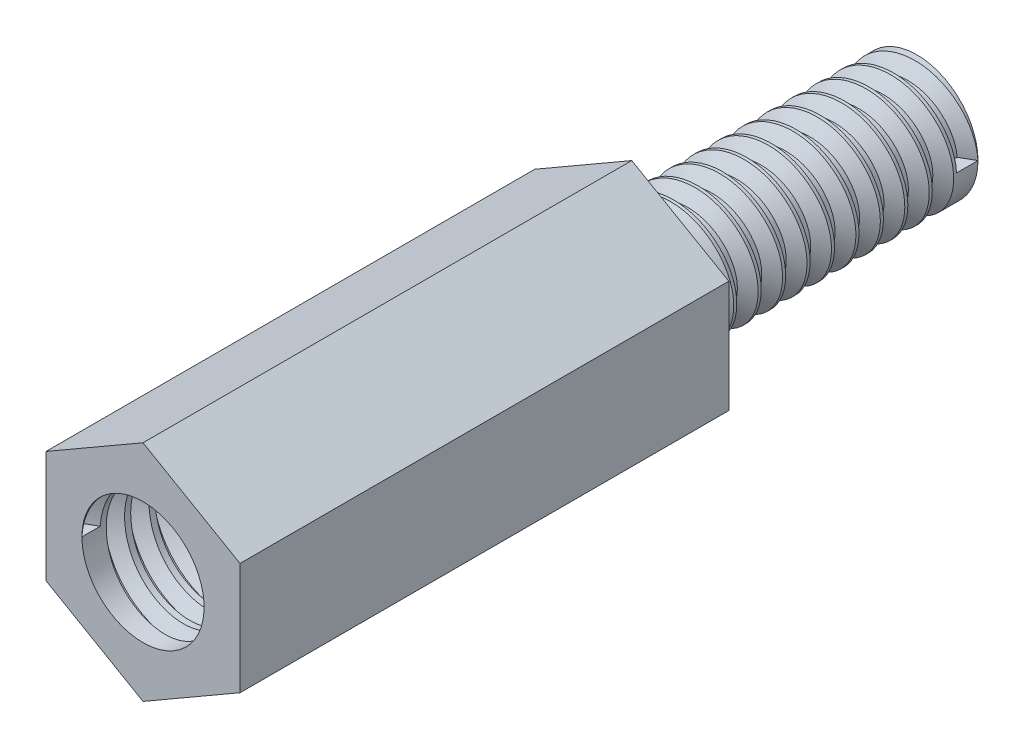
SolidWorks part; units mm, degrees
ref_plane "Front Plane" through (0, 0, 0) normal (0, 0, 1) x (1, 0, 0)
ref_plane "Top Plane" through (0, 0, 0) normal (0, 1, 0) x (1, 0, 0)
ref_plane "Right Plane" through (0, 0, 0) normal (1, 0, 0) x (0, 0, -1)
sketch "Sketch1" plane through (0, 0, 0) normal (0, 0, 1) x (1, 0, 0)
  line L1 (-2.3816, -1.375) -> (0, -2.75)
  line L2 (0, -2.75) -> (2.3816, -1.375)
  line L3 (2.3816, -1.375) -> (2.3816, 1.375)
  line L4 (2.3816, 1.375) -> (0, 2.75)
  line L5 (0, 2.75) -> (-2.3816, 1.375)
  line L6 (-2.3816, 1.375) -> (-2.3816, -1.375)
  circle A0 centre (0, 0) radius 2.3816 construction
  dimension "D1" = 5.5
extrude "Boss-Extrude1" add sketch "Sketch1" along normal blind 12
sketch "Sketch2" plane through (0, 0, 12) normal (0, 0, 1) x (1, 0, 0)
  circle A0 centre (0, 0) radius 1.5
  dimension "D1" = 3
extrude "Cut-Extrude1" cut sketch "Sketch2" against normal blind 7
sketch "Sketch3" plane through (0, 0, 0) normal (0, 0, -1) x (-1, 0, 0)
  circle A0 centre (0, 0) radius 1.5
  dimension "D1" = 3
extrude "Boss-Extrude2" add sketch "Sketch3" along normal blind 7
thread "Thread1" pitch 0.6 method cut profile "Thread Profile1" start angle 0, offset 0, length 0, pitch 0.6, diameter 3
ref_plane "Plane1" through (1.5, 0, -7) normal (0, -1, 0) x (1, 0, 0)
sketch "Thread Profile1" plane through (1.5, 0, -7) normal (0, -1, 0) x (1, 0, 0)
  line L0 (0, 0) -> (0, 0.6) construction
  line L11 (0, 0) -> (0, 0.525)
  line L12 (0, 0.525) -> (-0.3248, 0.3375)
  line L13 (-0.3248, 0.3375) -> (-0.3248, 0.1875)
  line L15 (-0.3248, 0.1875) -> (0, 0)
  line L17 (-0.3248, 0.2625) -> (0, 0.2625) construction
  point P2 (0, 0)
  dimension "Pitch" = 0.6
  dimension "Profile_Angle" = 60
  dimension "Profile_Land" = 0.15
  dimension "Profile_Height" = 0.3248
thread "Thread2" pitch 0.6 method cut profile "Thread Profile2" start angle 0, offset 0, length 0, pitch 0.6, diameter 3
ref_plane "Plane2" through (-1.5, 0, 12) normal (0, -1, 0) x (-1, 0, 0)
sketch "Thread Profile2" plane through (-1.5, 0, 12) normal (0, -1, 0) x (-1, 0, 0)
  line L0 (0, 0) -> (0, 0.6) construction
  line L1 (0, 0) -> (0.3248, 0.1875)
  line L2 (0.3248, 0.1875) -> (0.3248, 0.2625)
  line L3 (0.3248, 0.2625) -> (0, 0.45)
  line L4 (0.3248, 0.225) -> (0, 0.225) construction
  line L11 (0, 0) -> (0, 0.45)
  point P2 (0, 0)
  dimension "Pitch" = 0.6
  dimension "Profile_Angle" = 60
  dimension "Profile_Land" = 0.075
  dimension "Profile_Height" = 0.3248
